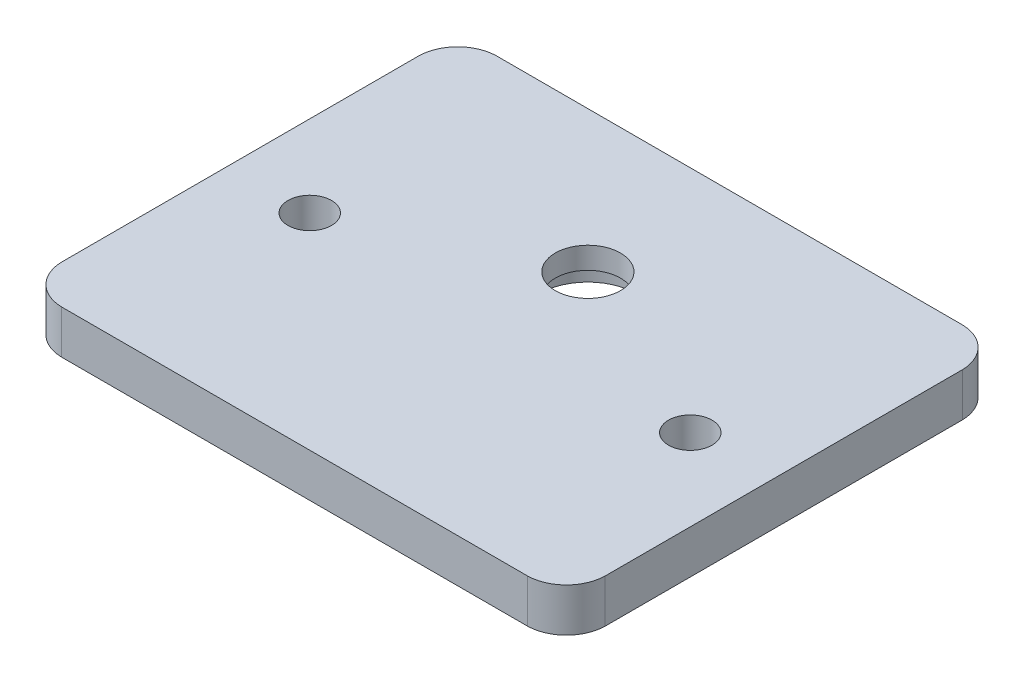
SolidWorks part; units mm, degrees
ref_plane "Front Plane" through (0, 0, 0) normal (0, 0, 1) x (1, 0, 0)
ref_plane "Top Plane" through (0, 0, 0) normal (0, 1, 0) x (1, 0, 0)
ref_plane "Right Plane" through (0, 0, 0) normal (1, 0, 0) x (0, 0, -1)
sketch "Sketch1" plane through (0, 0, 0) normal (0, 1, 0) x (1, 0, 0)
  line L0 (0, -3.7692) -> (0, -12.0494) construction
  line L5 (-25, 20) -> (25, 20)
  line L6 (-25, 20) -> (-25, -20)
  line L7 (-25, -20) -> (25, -20)
  line L8 (25, 20) -> (25, -20)
  line L9 (-25, 20) -> (25, -20) construction
  line L10 (-25, -20) -> (25, 20) construction
  line L11 (-5.3094, 0) -> (-10.9893, 0) construction
  arc A3 (-25, -16.277) -> (-21.447, -20) centre (-21.362, -16.362) ccw
  arc A4 (-25, 16.277) -> (-21.447, 20) centre (-21.362, 16.362) cw
  arc A5 (25, 16.277) -> (21.447, 20) centre (21.362, 16.362) ccw
  arc A6 (25, -16.277) -> (21.447, -20) centre (21.362, -16.362) cw
  circle A7 centre (-0.0217, 6.9999) radius 4.5
  circle A8 centre (0, 0) radius 14
  circle A9 centre (-17.5, -1.1027) radius 2
  circle A10 centre (17.5, -1.1027) radius 2
  circle A11 centre (-0.0217, 6.9999) radius 3
  point P0 (0, 0)
  point P30 (0, 0)
  dimension "D1" = 50
  dimension "D2" = 40
extrude "Boss-Extrude2" add sketch "Sketch1" along normal blind 4 contours A6 L8 A5 L5 A4 L6 A3 L7 A10 A9 A8 | A8 A7 | A7 A11 | A11 region at (0, 0, -19.3597) region at (-4.3944, 0, -6.9999) region at (0.0025, 0, 0.8065) region at (-0.0217, 0, -6.9999)
extrude "Cut-Extrude2" cut sketch "Sketch1<14>" along normal through all contours A11
sketch "Sketch1<14>" plane through (0, 0, 0) normal (0, 1, 0) x (1, 0, 0) same geometry as "Sketch1"
extrude "Cut-Extrude3" cut sketch "Sketch1<15>" along normal blind 2 contours A7
sketch "Sketch1<15>" plane through (0, 0, 0) normal (0, 1, 0) x (1, 0, 0) same geometry as "Sketch1"
